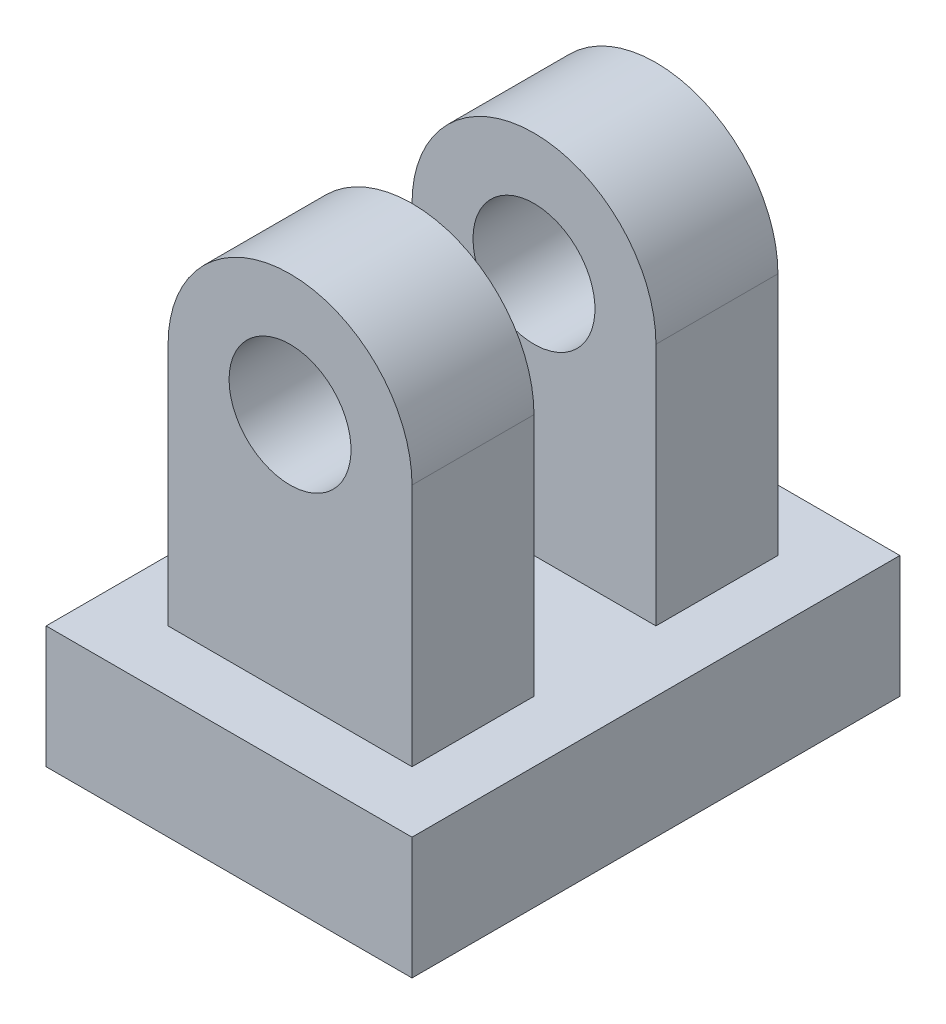
SolidWorks part; units mm, degrees
ref_plane "Front Plane" through (0, 0, 0) normal (0, 0, 1) x (1, 0, 0)
ref_plane "Top Plane" through (0, 0, 0) normal (0, 1, 0) x (1, 0, 0)
ref_plane "Right Plane" through (0, 0, 0) normal (1, 0, 0) x (0, 0, -1)
sketch "Sketch1" plane through (0, 0, 0) normal (0, 1, 0) x (1, 0, 0)
  line L1 (-1.5, 2) -> (1.5, 2)
  line L2 (-1.5, 2) -> (-1.5, -2)
  line L3 (-1.5, -2) -> (1.5, -2)
  line L4 (1.5, 2) -> (1.5, -2)
  line L5 (-1.5, 2) -> (1.5, -2) construction
  line L6 (-1.5, -2) -> (1.5, 2) construction
  line L7 (-1, 1.5) -> (1, 1.5)
  line L8 (-1, 1.5) -> (-1, 0.5)
  line L9 (-1, 0.5) -> (1, 0.5)
  line L10 (1, 1.5) -> (1, 0.5)
  line L11 (-1, 1.5) -> (1, 0.5) construction
  line L12 (-1, 0.5) -> (1, 1.5) construction
  line L13 (-1, -0.5) -> (1, -0.5)
  line L14 (-1, -0.5) -> (-1, -1.5)
  line L15 (-1, -1.5) -> (1, -1.5)
  line L16 (1, -0.5) -> (1, -1.5)
  line L17 (-1, -0.5) -> (1, -1.5) construction
  line L18 (-1, -1.5) -> (1, -0.5) construction
  point P0 (0, 0)
  point P6 (0, 1)
  point P11 (0, -1)
  dimension "D1" = 3
  dimension "D2" = 4
  dimension "D3" = 2
  dimension "D4" = 2
  dimension "D5" = 1
  dimension "D6" = 1
  dimension "D7" = 0.5
  dimension "D8" = 0.5
extrude "Boss-Extrude1" add sketch "Sketch1" against normal blind 1 contours L4 L1 L2 L3 L7 L10 L9 L8 L13 L16 L15 L14 | L16 L13 L14 L15 | L10 L7 L8 L9 region at (0, 0, 0) region at (0, 0, -1) region at (0, 0, 1)
extrude "Boss-Extrude2" add sketch "Sketch1<3>" along normal blind 3 contours L16 L13 L14 L15 | L10 L7 L8 L9 region at (0, 0, -1) region at (0, 0, 1)
sketch "Sketch1<3>" plane through (0, 0, 0) normal (0, 1, 0) x (1, 0, 0) same geometry as "Sketch1"
sketch "Sketch2" plane through (0, 0, -1.5) normal (0, 0, -1) x (-1, 0, 0)
  line L0 (1, 3) -> (-1, 3) construction
  line L1 (-1, 3) -> (-1, 0) construction
  line L6 (-1, 0) -> (1, 0)
  line L7 (1, 0) -> (1, 3)
  line L8 (1, 3) -> (-1, 3)
  line L9 (-1, 3) -> (-1, 0)
  line L10 (-1, 0) -> (1, 0)
  line L11 (1, 0) -> (1, 3)
  line L12 (1, 3) -> (-1, 3)
  line L13 (-1, 3) -> (-1, 0)
  circle A0 centre (0, 2) radius 1
  circle A1 centre (0, 2) radius 0.5
  line M7 (1, 3) -> (-1, 3)
  line M8 (-1, 3) -> (-1, 0)
  dimension "D1" = 2
  dimension "D3" = 1
  dimension "D2" = 0
extrude "Cut-Extrude1" cut sketch "Sketch2" against normal blind 3 contours A0 L12 M8 | A0 L11 M7 | A1 region at (0.7766, 2.7766, -1.5) region at (-0.7766, 2.7766, -1.5) region at (0, 2, -1.5)
